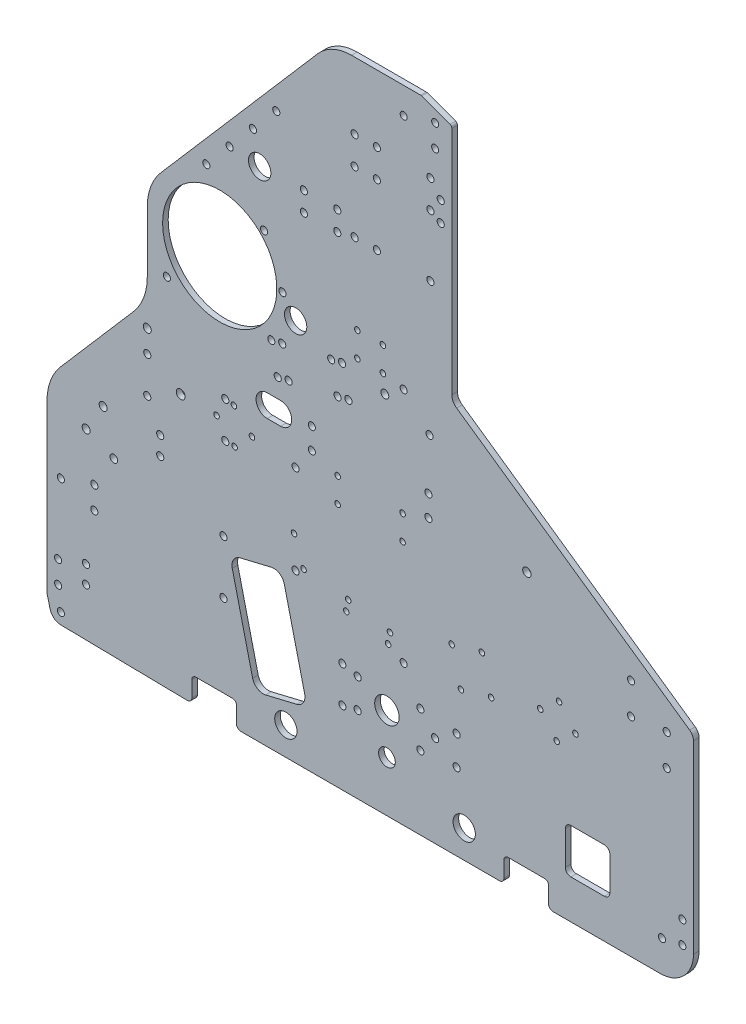
SolidWorks part; units mm, degrees
ref_plane "Front Plane" through (0, 0, 0) normal (0, 0, 1) x (1, 0, 0)
ref_plane "Top Plane" through (0, 0, 0) normal (0, 1, 0) x (1, 0, 0)
ref_plane "Right Plane" through (0, 0, 0) normal (1, 0, 0) x (0, 0, -1)
sketch "Sketch1" plane through (0, 0, 0) normal (0, 0, 1) x (1, 0, 0)
  line L0 (82.55, -20.32) -> (82.55, -6.35)
  line L2 (0, 0) -> (0, 157.48)
  line L4 (368.3, -20.32) -> (368.3, 106.68)
  line L5 (82.55, -6.35) -> (107.95, -6.35)
  line L6 (107.95, -6.35) -> (107.95, -20.32)
  line L7 (107.95, -20.32) -> (260.35, -20.32)
  line L8 (260.35, -20.32) -> (260.35, -6.35)
  line L9 (260.35, -6.35) -> (285.75, -6.35)
  line L10 (285.75, -6.35) -> (285.75, -20.32)
  line L11 (285.75, -20.32) -> (368.3, -20.32)
  line L12 (361.95, 12.7) -> (368.3, 12.7) construction
  line L13 (0, 0) -> (6.35, 0) construction
  line L14 (0.1896, -7.8901) -> (1.7771, -14.2401)
  line L15 (7.8295, -19.0491) -> (82.55, -20.32)
  line L16 (0, 0) -> (0, -6.35)
  line L17 (76.2, 128.905) -> (79.375, 128.905) construction
  line L18 (57.15, 118.5863) -> (101.6, 118.5862) construction
  line L19 (57.15, 118.5863) -> (57.15, 139.2238) construction
  line L20 (101.6, 118.5862) -> (101.6, 139.2237) construction
  line L21 (57.15, 139.2238) -> (101.6, 139.2237) construction
  line L22 (57.15, 118.5863) -> (101.6, 139.2237) construction
  line L23 (101.6, 118.5862) -> (57.15, 139.2238) construction
  line L24 (101.6, 139.2237) -> (125.4682, 147.9111) construction
  line L25 (203.2, 59.805) -> (203.2, 194.805) construction
  line L26 (203.2, 194.805) -> (203.2, 329.805) construction
  line L27 (355.6, 332.105) -> (330.2, 332.105) construction
  line L28 (330.2, 332.105) -> (330.2, 217.805) construction
  line L29 (330.2, 217.805) -> (355.6, 217.805) construction
  line L30 (355.6, 217.805) -> (355.6, 332.105) construction
  line L31 (203.2, 344.805) -> (203.2, 194.805) construction
  line L32 (50.8, 332.105) -> (76.2, 332.105) construction
  line L33 (76.2, 332.105) -> (76.2, 217.805) construction
  line L34 (50.8, 217.805) -> (50.8, 332.105) construction
  line L35 (76.2, 217.805) -> (50.8, 217.805) construction
  line L36 (213.2, 344.805) -> (230.6638, 338.455)
  line L37 (203.2, 344.805) -> (161.925, 344.805)
  line L38 (203.2, 344.805) -> (213.2, 344.805)
  line L39 (348.5362, 344.805) -> (413.4623, 344.805)
  line L40 (348.5362, 344.805) -> (230.6638, 344.805) construction
  line L42 (161.925, 344.805) -> (0, 157.48)
  line L44 (230.6638, 338.455) -> (230.6638, 202.565)
  line L45 (230.6638, 202.565) -> (368.3, 106.68)
  line L46 (213.2, 344.805) -> (-141.0713, 344.805) construction
  line L47 (350.3395, -2.3595) -> (368.3, -20.32) construction
  line L48 (125.4682, 147.9111) -> (133.0882, 147.9111) construction
  line L49 (125.4682, 154.2611) -> (133.0882, 154.2611)
  line L50 (125.4682, 141.5611) -> (133.0882, 141.5611)
  circle A0 centre (6.35, 0) radius 2.032
  circle A1 centre (6.35, 12.7) radius 2.032
  circle A2 centre (361.95, 0) radius 2.032
  circle A3 centre (361.95, 12.7) radius 2.032
  arc A5 (1.7771, -14.2401) -> (7.8295, -19.0491) centre (7.9375, -12.7) ccw
  circle A6 centre (7.9375, -12.7) radius 2.032
  arc A7 (0, -6.35) -> (0.1896, -7.8901) centre (6.35, -6.35) ccw
  circle A8 centre (38.1, 78.105) radius 2.032
  circle A9 centre (76.2, 128.905) radius 2.54
  circle A10 centre (101.6, 118.5862) radius 2.032
  circle A11 centre (101.6, 139.2237) radius 2.032
  circle A12 centre (57.15, 139.2238) radius 2.032
  circle A13 centre (57.15, 118.5863) radius 2.032
  circle A15 centre (203.2, 59.805) radius 2
  circle A16 centre (203.2, 194.805) radius 2
  circle A17 centre (203.2, 329.805) radius 2
  circle A18 centre (63.5, 313.055) radius 2.032
  circle A20 centre (355.6, 332.105) radius 2.032
  circle A21 centre (330.2, 332.105) radius 2.032
  circle A22 centre (355.6, 217.805) radius 2.032
  circle A23 centre (330.2, 217.805) radius 2.032
  circle A24 centre (50.8, 332.105) radius 2.032
  circle A25 centre (76.2, 332.105) radius 2.032
  circle A26 centre (50.8, 217.805) radius 2.032
  circle A27 centre (76.2, 217.805) radius 2.032
  circle A28 centre (221.1381, 335.28) radius 2
  circle A29 centre (224.3138, 298.831) radius 2.032
  circle A30 centre (353.06, 100.7351) radius 2.032
  circle A31 centre (332.74, 115.9751) radius 2.032
  circle A32 centre (332.74, 98.1951) radius 2.032
  circle A33 centre (353.06, 82.9551) radius 2.032
  circle A34 centre (117.3562, 280.4276) radius 2.032
  circle A35 centre (104.0678, 265.0548) radius 2.032
  circle A36 centre (90.7795, 249.682) radius 2.032
  circle A38 centre (130.6445, 295.8004) radius 2.032
  circle A39 centre (68.326, 182.9237) radius 2.032
  circle A40 centre (224.3138, 287.401) radius 2.032
  circle A41 centre (125.4682, 147.9111) radius 6.35
  circle A42 centre (221.1381, 322.58) radius 2
  circle A43 centre (350.3395, -2.3595) radius 2.032
  arc A44 (125.4682, 154.2611) -> (125.4682, 141.5611) centre (125.4682, 147.9111) ccw
  arc A45 (133.0882, 141.5611) -> (133.0882, 154.2611) centre (133.0882, 147.9111) ccw
  point P82 (203.2, 344.805)
  point P90 (368.3, 62.484)
  point P107 (129.2782, 147.9111)
  dimension "D6" = 4.064
  dimension "D10" = 6.35
  dimension "D11" = 4.064
  dimension "D17" = 38.1
  dimension "D27" = 4
  dimension "D31" = 4.064
  dimension "D32" = 41.275
  dimension "D36" = 4.064
  dimension "D47" = 39.624
  dimension "D48" = 4.064
  dimension "D25" = 5.08
  dimension "D26" = 4.064
  dimension "D52" = 4.064
  dimension "D65" = 4.064
  dimension "D69" = 4.064
  dimension "D72" = 12.7
  dimension "D77" = 6.35
  dimension "D2" = 127
  dimension "D3" = 13.97
  dimension "D4" = 25.4
  dimension "D5" = 152.4
  dimension "D7" = 12.7
  dimension "D8" = 6.35
  dimension "D9" = 20.32
  dimension "D12" = 12.7
  dimension "D13" = 1.5875
  dimension "D14" = 82.55
  dimension "D15" = 368.3
  dimension "D16" = 6.35
  dimension "D18" = 98.425
  dimension "D19" = 38.1
  dimension "D20" = 50.8
  dimension "D21" = 3.175
  dimension "D22" = 270
  dimension "D23" = 20.6375
  dimension "D24" = 44.45
  dimension "D28" = 135
  dimension "D29" = 12.7
  dimension "D30" = 15
  dimension "D33" = 63.5
  dimension "D34" = 27.4638
  dimension "D35" = 12.7
  dimension "D37" = 114.3
  dimension "D38" = 25.4
  dimension "D39" = 12.7
  dimension "D40" = 157.48
  dimension "D41" = 142.24
  dimension "D42" = 365.125
  dimension "D43" = 10
  dimension "D44" = 6.35
  dimension "D45" = 31.75
  dimension "D46" = 3.175
  dimension "D49" = 6.35
  dimension "D50" = 203.2
  dimension "D51" = 15.24
  dimension "D53" = 17.78
  dimension "D54" = 17.78
  dimension "D55" = 20.32
  dimension "D56" = 15.24
  dimension "D57" = 92.202
  dimension "D58" = 8.382
  dimension "D59" = 20.32
  dimension "D60" = 20.32
  dimension "D61" = 8.382
  dimension "D62" = 20.32
  dimension "D63" = 8.382
  dimension "D64" = 8.382
  dimension "D66" = 35.052
  dimension "D67" = 68.326
  dimension "D68" = 11.43
  dimension "D70" = 25.4
  dimension "D71" = 110
  dimension "D73" = 17.9381
  dimension "D74" = 12.7
  dimension "D75" = 45
  dimension "D76" = 25.4
  dimension "D79" = 7.62
extrude "Boss-Extrude1" add sketch "Sketch1" along normal blind 3.175 contours L16 A7 L14 A5 L15 L2 A0 A1 A6 region at (171.4194, 119.4541, 0)
fillet "Fillet1" radius 2.286 4 edges at (285.75, -6.35, 1.5875) (107.95, -6.35, 1.5875) (260.35, -6.35, 1.5875) (82.55, -6.35, 1.5875)
fillet "Fillet2" radius 6.35 1 edges at (230.6638, 202.565, 1.5875)
sketch "Sketch2" plane through (0, 0, 0) normal (0, 0, -1) x (-1, 0, 0)
  circle A0 centre (-100.5528, 71.086) radius 2.032 construction
  circle A1 centre (-100.5528, 40.606) radius 2.032 construction
  circle A2 centre (-22.225, 18.2025) radius 2.032 construction
  circle A3 centre (-22.225, 8.0425) radius 2.032 construction
  circle A4 centre (-100.5528, 71.086) radius 2.032
  circle A5 centre (-100.5528, 40.606) radius 2.032
  circle A6 centre (-22.225, 18.2025) radius 2.032
  circle A7 centre (-22.225, 8.0425) radius 2.032
extrude "Cut-Extrude1" cut sketch "Sketch2" against normal through all
fillet "Fillet3" radius 1.5875 2 edges at (230.6638, 338.455, 1.5875) (213.2, 344.805, 1.5875)
sketch "Sketch3" plane through (0, 0, 3.175) normal (0, 0, 1) x (1, 0, 0)
  line L0 (132.9524, 63.2646) -> (132.7215, 64.2281) construction
  line L1 (128.3814, 66.8897) -> (110.6828, 62.6472) construction
  line L2 (114.5132, 58.4237) -> (126.8822, 61.3887) construction
  line L3 (108.0212, 58.3071) -> (108.2522, 57.3436) construction
  line L4 (131.2006, 57.703) -> (140.0164, 20.9265) construction
  line L5 (144.0993, 16.7636) -> (132.9524, 63.2646) construction
  line L6 (108.2522, 57.3436) -> (119.3991, 10.8426) construction
  line L7 (121.1509, 16.4042) -> (112.3351, 53.1807) construction
  line L8 (119.3991, 10.8426) -> (119.6301, 9.8791) construction
  line L9 (144.3303, 15.8001) -> (144.0993, 16.7636) construction
  line L10 (137.8383, 15.6835) -> (125.4694, 12.7185) construction
  line L11 (123.9701, 7.2175) -> (141.6687, 11.4601) construction
  line L12 (132.9524, 63.2646) -> (132.7215, 64.2281)
  line L13 (128.3814, 66.8897) -> (110.6828, 62.6472)
  line L14 (114.5132, 58.4237) -> (126.8822, 61.3887)
  line L15 (108.0212, 58.3071) -> (108.2522, 57.3436)
  line L16 (131.2006, 57.703) -> (140.0164, 20.9265)
  line L17 (144.0993, 16.7636) -> (132.9524, 63.2646)
  line L18 (108.2522, 57.3436) -> (119.3991, 10.8426)
  line L19 (121.1509, 16.4042) -> (112.3351, 53.1807)
  line L20 (119.3991, 10.8426) -> (119.6301, 9.8791)
  line L21 (144.3303, 15.8001) -> (144.0993, 16.7636)
  line L22 (137.8383, 15.6835) -> (125.4694, 12.7185)
  line L23 (123.9701, 7.2175) -> (141.6687, 11.4601)
  line L24 (127.7894, 69.3598) -> (110.0908, 65.1172)
  line L25 (105.5512, 57.715) -> (105.7822, 56.7515)
  line L26 (105.7822, 56.7515) -> (116.9291, 10.2505)
  line L27 (116.9291, 10.2505) -> (117.16, 9.287)
  line L28 (124.5622, 4.7475) -> (142.2608, 8.99)
  line L29 (146.8003, 16.3922) -> (146.5694, 17.3557)
  line L30 (146.5694, 17.3557) -> (135.4225, 63.8567)
  line L31 (135.4225, 63.8567) -> (135.1915, 64.8202)
  line L32 (14.605, -0.1369) -> (103.7278, 32.3011) construction
  line L33 (14.605, -0.1369) -> (103.7278, 32.3011)
  line L34 (0, -6.35) -> (0, 157.48) construction
  line L35 (-39.6666, 74.7152) -> (103.7278, 126.9065) construction
  line L36 (26.9875, 46.9531) -> (26.9875, 59.6531) construction
  line L37 (107.95, -20.32) -> (260.35, -20.32) construction
  line L38 (64.5259, 92.5258) -> (64.5259, 102.9405) construction
  line L39 (131.6538, 14.201) -> (136.0946, -4.3242) construction
  line L40 (136.0946, -4.3242) -> (237.6946, -4.3242) construction
  arc A0 (132.7215, 64.2281) -> (128.6308, 66.9403) centre (129.2206, 63.3889) ccw construction
  arc A1 (110.6828, 62.6472) -> (110.4377, 62.5791) centre (111.522, 59.1463) ccw construction
  arc A2 (128.6308, 66.9403) -> (128.3814, 66.8897) centre (129.2206, 63.3889) ccw construction
  arc A3 (110.4377, 62.5791) -> (108.0212, 58.3071) centre (111.522, 59.1463) ccw construction
  arc A4 (119.6301, 9.8791) -> (123.7207, 7.1669) centre (123.1309, 10.7183) ccw construction
  arc A5 (141.9139, 11.5281) -> (144.3303, 15.8001) centre (140.8295, 14.9609) ccw construction
  arc A6 (141.6687, 11.4601) -> (141.9139, 11.5281) centre (140.8295, 14.9609) ccw construction
  arc A7 (123.7207, 7.1669) -> (123.9701, 7.2175) centre (123.1309, 10.7183) ccw construction
  arc A8 (132.7215, 64.2281) -> (128.6308, 66.9403) centre (129.2206, 63.3889) ccw
  arc A9 (110.6828, 62.6472) -> (110.4377, 62.5791) centre (111.522, 59.1463) ccw
  arc A10 (128.6308, 66.9403) -> (128.3814, 66.8897) centre (129.2206, 63.3889) ccw
  arc A11 (110.4377, 62.5791) -> (108.0212, 58.3071) centre (111.522, 59.1463) ccw
  arc A12 (119.6301, 9.8791) -> (123.7207, 7.1669) centre (123.1309, 10.7183) ccw
  arc A13 (141.9139, 11.5281) -> (144.3303, 15.8001) centre (140.8295, 14.9609) ccw
  arc A14 (141.6687, 11.4601) -> (141.9139, 11.5281) centre (140.8295, 14.9609) ccw
  arc A15 (123.7207, 7.1669) -> (123.9701, 7.2175) centre (123.1309, 10.7183) ccw
  arc A16 (110.0908, 65.1172) -> (109.6726, 65.0012) centre (111.522, 59.1463) ccw
  arc A17 (109.6726, 65.0012) -> (105.5512, 57.715) centre (111.522, 59.1463) ccw
  arc A18 (117.16, 9.287) -> (124.1369, 4.6613) centre (123.1309, 10.7183) ccw
  arc A19 (124.1369, 4.6613) -> (124.5622, 4.7475) centre (123.1309, 10.7183) ccw
  arc A20 (142.2608, 8.99) -> (142.6789, 9.1061) centre (140.8295, 14.9609) ccw
  arc A21 (142.6789, 9.1061) -> (146.8003, 16.3922) centre (140.8295, 14.9609) ccw
  arc A22 (135.1915, 64.8202) -> (128.2147, 69.446) centre (129.2206, 63.3889) ccw
  arc A23 (128.2147, 69.446) -> (127.7894, 69.3598) centre (129.2206, 63.3889) ccw
  circle A24 centre (136.0946, -4.3242) radius 6.35
  circle A25 centre (237.6946, -4.3242) radius 6.35
  circle A26 centre (134.1438, 208.2281) radius 2.032 construction
  circle A33 centre (26.9875, 46.9531) radius 2.032
  circle A34 centre (26.9875, 59.6531) radius 2.032
  circle A35 centre (7.9375, 53.3031) radius 2.032
  circle A37 centre (32.0306, 100.8109) radius 32.385 construction
  circle A38 centre (32.0306, 100.8109) radius 2.286
  circle A39 centre (123.682, 233.4851) radius 2.032 construction
  circle A40 centre (64.5259, 102.9405) radius 2.032
  circle A41 centre (64.5259, 92.5258) radius 2.032
  circle A42 centre (134.1438, 208.2281) radius 2.032
  circle A43 centre (123.682, 233.4851) radius 2.032
  ellipse E0 centre (124.5974, 48.8487) end of major axis (128.5376, 61.3578) minor radius 6 (131.2006, 57.703) -> (126.8822, 61.3887) ccw construction
  ellipse E1 centre (122.2349, 48.2824) end of major axis (113.0518, 57.6456) minor radius 6 (114.5132, 58.4237) -> (112.3351, 53.1807) ccw construction
  ellipse E2 centre (127.7541, 25.2585) end of major axis (131.6942, 37.7675) minor radius 6 (121.1509, 16.4042) -> (125.4694, 12.7185) ccw construction
  ellipse E3 centre (130.1166, 25.8248) end of major axis (139.2998, 16.4616) minor radius 6 (137.8383, 15.6835) -> (140.0164, 20.9265) ccw construction
  ellipse E4 centre (124.5974, 48.8487) end of major axis (120.6573, 36.3397) minor radius 6 (131.2006, 57.703) -> (126.8822, 61.3887) ccw
  ellipse E5 centre (122.2349, 48.2824) end of major axis (131.4181, 38.9192) minor radius 6 (114.5132, 58.4237) -> (112.3351, 53.1807) ccw
  ellipse E6 centre (127.7541, 25.2585) end of major axis (131.6942, 37.7675) minor radius 6 (121.1509, 16.4042) -> (125.4694, 12.7185) ccw
  ellipse E7 centre (130.1166, 25.8248) end of major axis (139.2998, 16.4616) minor radius 6 (137.8383, 15.6835) -> (140.0164, 20.9265) ccw
  point P93 (26.9875, 53.3031)
  point P115 (32.0306, 100.8109)
  dimension "D3" = 64.77
  dimension "D4" = 4.572
  dimension "D8" = 4.064
  dimension "D13" = 12.7
  dimension "D15" = 101.6
  dimension "D2" = 88.9
  dimension "D5" = 7.9375
  dimension "D6" = 19.05
  dimension "D7" = 73.6231
  dimension "D9" = 12.7
  dimension "D10" = 10.4147
  dimension "D11" = 37.5384
  dimension "D12" = 45.5727
  dimension "D14" = 19.05
  dimension "D1" = 2.54
extrude "Cut-Extrude2" cut sketch "Sketch3" against normal through all contours A22 A23 L24 A16 A17 L25 L26 L27 A18 A19 L28 A20 A21 L29 L30 L31 A15 A12 L20 L18 L15 A11 A9 L13 A10 A8 L12 L17 L21 A13 A14 L23 | A12 A15 L23 A14 A13 L21 L17 L12 A8 A10 L13 A9 A11 L15 L18 L20 E7 L22 E6 L19 E5 L14 E4 L16 | L22 E7 L16 E4 L14 E5 L19 E6 | A38 | A41 | A40 | A35 | A34 | A33 | A43 | A42 | A24 | A25 region at (137.844, 39.8506, 3.175) region at (126.1758, 37.0536, 3.175) region at (128.1544, 68.6507, 3.175) region at (32.0306, 100.8109, 3.175) region at (64.5259, 102.9405, 3.175) region at (64.5259, 92.5258, 3.175)
sketch "Sketch4" plane through (0, 0, 3.175) normal (0, 0, 1) x (1, 0, 0)
  line L0 (57.15, 139.2238) -> (101.6, 139.2237) construction
  line L1 (168.275, 21.4312) -> (212.725, 21.4312) construction
  line L2 (168.275, 21.4312) -> (168.275, 42.0687) construction
  line L3 (168.275, 42.0687) -> (212.725, 42.0687) construction
  line L4 (212.725, 21.4312) -> (212.725, 42.0687) construction
  line L5 (168.275, 21.4312) -> (212.725, 42.0687) construction
  line L6 (168.275, 42.0687) -> (212.725, 21.4312) construction
  line L7 (57.15, 118.5863) -> (57.15, 139.2238) construction
  line L8 (107.95, -20.32) -> (260.35, -20.32) construction
  line L9 (193.675, 31.75) -> (177.005, 31.75) construction
  line L10 (190.5, 31.75) -> (193.675, 31.75) construction
  line L11 (6.35, 12.7) -> (361.95, 12.7) construction
  line L12 (107.95, -6.35) -> (107.95, -20.32) construction
  line L13 (193.675, 31.75) -> (220.6625, 31.75) construction
  line L14 (177.005, 23.4569) -> (177.005, 40.0431) construction
  line L15 (213.2, 44.805) -> (193.2, 44.805) construction
  line L16 (213.2, 44.805) -> (213.2, 344.805) construction
  line L17 (213.2, 344.805) -> (193.2, 344.805) construction
  line L18 (193.2, 44.805) -> (193.2, 344.805) construction
  line L19 (213.2, 44.805) -> (193.2, 344.805) construction
  line L20 (213.2, 344.805) -> (193.2, 44.805) construction
  line L21 (226.1381, 335.28) -> (226.1381, 31.75) construction
  line L22 (237.33, 40.0431) -> (233.3612, 40.0431) construction
  line L23 (237.33, 23.4569) -> (233.3612, 23.4569) construction
  circle A0 centre (168.275, 42.0687) radius 2.032
  circle A1 centre (212.725, 42.0687) radius 2.032
  circle A2 centre (212.725, 21.4312) radius 2.032
  circle A3 centre (168.275, 21.4312) radius 2.032
  circle A4 centre (193.675, 31.75) radius 6.985
  circle A7 centre (220.6625, 31.75) radius 14.2875 construction
  circle A8 centre (193.675, 31.75) radius 12.7 construction
  circle A9 centre (177.005, 40.0431) radius 2.032
  circle A10 centre (177.005, 23.4569) radius 2.032
  circle A11 centre (237.33, 40.0431) radius 2.032 construction
  circle A12 centre (237.33, 23.4569) radius 2.032 construction
  circle A13 centre (193.675, 8.4667) radius 4.7625
  circle A14 centre (221.1381, 31.75) radius 2.032
  circle A15 centre (221.1381, 31.75) radius 5 construction
  circle A16 centre (221.1381, 335.28) radius 5 construction
  circle A17 centre (233.3612, 23.4569) radius 2.032
  circle A18 centre (233.3612, 40.0431) radius 2.032
  point P0 (190.5, 31.75)
  point P26 (203.2, 194.805)
  point P38 (177.005, 31.75)
  dimension "D1" = 4.064
  dimension "D4" = 13.97
  dimension "D7" = 9.525
  dimension "D10" = 25.4
  dimension "D11" = 28.575
  dimension "D16" = 10
  dimension "D17" = 4.064
  dimension "D18" = 10
  dimension "D2" = 52.07
  dimension "D3" = 3.175
  dimension "D5" = 82.55
  dimension "D6" = 26.9875
  dimension "D8" = 20
  dimension "D9" = 300
  dimension "D12" = 16.67
  dimension "D13" = 16.5862
  dimension "D14" = 60.325
  dimension "D15" = 23.2833
  dimension "D19" = 3.9688
extrude "Cut-Extrude3" cut sketch "Sketch4" against normal through all
sketch "Sketch5" plane through (0, 0, 0) normal (0, 0, -1) x (-1, 0, 0)
  line L0 (-57.15, 223.5947) -> (-57.15, 165.3337)
  line L1 (-161.925, 344.805) -> (-52.7201, 218.4699) construction
  line L2 (-57.15, 165.3337) -> (0, 99.219)
  line L3 (0, -6.35) -> (0, 157.48) construction
  line L4 (-147.864, -30.311) -> (-147.864, -16.0874)
  line L5 (-50.4199, 215.8089) -> (0, 157.48) construction
  line L6 (-57.15, 223.5947) -> (0, 157.48)
  line L7 (0, 157.48) -> (0, 99.219)
  line L8 (-98.425, 208.2281) -> (-141.6756, 197.9719) construction
  line L9 (-368.3, -20.32) -> (-368.3, 106.68) construction
  line L10 (-285.75, -20.32) -> (-368.3, -20.32) construction
  circle A0 centre (-98.425, 208.2281) radius 32.5437
  circle A1 centre (-141.6756, 197.9719) radius 6.35
  circle A3 centre (-273.4056, 139.7279) radius 2.39
  dimension "D3" = 65.0875
  dimension "D7" = 12.7
  dimension "D8" = 4.78
  dimension "D1" = 38.1
  dimension "D2" = 57.15
  dimension "D4" = 41.275
  dimension "D5" = 41.275
  dimension "D6" = 94.8944
  dimension "D9" = 22.2382
  dimension "D10" = 160.0479
  dimension "D11" = 11.6447
  dimension "D14" = 62.5
  dimension "D13" = 44.45
extrude "Cut-Extrude5" cut sketch "Sketch5" against normal through all contours A0 | L7 L6 L0 L2 | A3 | A1 region at (28.575, 161.4068, 0) region at (98.425, 208.2281, 0) region at (273.4056, 139.7279, 0)
fillet "Fillet4" radius 31.75 3 edges at (0, 99.219, 1.5875) (57.15, 165.3337, 1.5875) (57.15, 223.5947, 1.5875)
sketch "Sketch6" plane through (0, 0, 3.175) normal (0, 0, 1) x (1, 0, 0)
  line L0 (285.75, -20.32) -> (368.3, -20.32) construction
  line L1 (298.45, 27.305) -> (317.5, 27.305)
  line L2 (295.275, 24.13) -> (295.275, 5.08)
  line L3 (298.45, 1.905) -> (317.5, 1.905)
  line L4 (320.675, 24.13) -> (320.675, 5.08)
  line L5 (295.275, 27.305) -> (320.675, 1.905) construction
  line L6 (295.275, 1.905) -> (320.675, 27.305) construction
  line L7 (368.3, -20.32) -> (368.3, 106.68) construction
  arc A0 (295.275, 5.08) -> (298.45, 1.905) centre (298.45, 5.08) ccw
  arc A1 (317.5, 1.905) -> (320.675, 5.08) centre (317.5, 5.08) ccw
  arc A2 (317.5, 27.305) -> (320.675, 24.13) centre (317.5, 24.13) cw
  arc A3 (298.45, 27.305) -> (295.275, 24.13) centre (298.45, 24.13) ccw
  point P0 (307.975, 14.605)
  dimension "D2" = 3.175
  dimension "D1" = 25.4
  dimension "D3" = 22.225
  dimension "D4" = 47.625
extrude "Cut-Extrude6" cut sketch "Sketch6" against normal through all
fillet "Fillet5" radius 25.4 1 edges at (161.925, 344.805, 1.5875)
sketch "Sketch8" plane through (0, 0, 0) normal (0, 0, -1) x (-1, 0, 0)
  line L0 (-230.6638, 337.343) -> (-230.6638, 205.8802) construction
  line L1 (-230.6638, 255.905) -> (-175.26, 255.905) construction
  line L2 (-175.26, 255.905) -> (-175.26, 306.705) construction
  line L3 (-175.26, 306.705) -> (-230.6638, 306.705) construction
  line L4 (-173.5432, 344.805) -> (-212.9203, 344.805) construction
  line L7 (-107.95, -20.32) -> (-260.35, -20.32) construction
  circle A0 centre (-218.44, 290.83) radius 3.9687
  circle A1 centre (-218.44, 290.83) radius 2.032
  circle A2 centre (218.44, 265.7972) radius 3.9687
  circle A3 centre (218.44, 265.7972) radius 2.032
  circle A4 centre (-205.74, 290.83) radius 3.9687
  circle A5 centre (-205.74, 290.83) radius 2.032
  circle A6 centre (-187.96, 290.83) radius 3.9687
  circle A7 centre (-187.96, 290.83) radius 2.032
  circle A8 centre (-187.96, 306.705) radius 2.032
  circle A9 centre (-175.26, 290.83) radius 3.9687
  circle A10 centre (-175.26, 290.83) radius 2.032
  circle A11 centre (-205.74, 306.705) radius 2.032
  circle A13 centre (-205.74, 255.905) radius 2.032
  circle A14 centre (-187.96, 255.905) radius 2.032
  circle A16 centre (-218.44, 306.705) radius 2.032
  circle A17 centre (-175.26, 306.705) radius 2.032
  circle A18 centre (-175.26, 255.905) radius 2.032
  circle A19 centre (-218.44, 255.905) radius 2.032
  circle A20 centre (-218.44, 306.705) radius 3.9687
  circle A21 centre (-205.74, 306.705) radius 3.9687
  circle A22 centre (-175.26, 306.705) radius 3.9687
  circle A23 centre (-218.44, 255.905) radius 3.9687
  circle A24 centre (-205.74, 255.905) radius 3.9687
  circle A25 centre (-187.96, 255.905) radius 3.9687
  circle A26 centre (-175.26, 255.905) radius 3.9687
  circle A27 centre (-187.96, 306.705) radius 3.9687
  dimension "D1" = 7.9375
  dimension "D7" = 4.064
  dimension "D13" = 12.2237
  dimension "D2" = 12.2237
  dimension "D3" = 12.7
  dimension "D4" = 17.78
  dimension "D5" = 12.7
  dimension "D6" = 88.9
  dimension "D8" = 38.1
  dimension "D9" = 17.78
  dimension "D10" = 12.7
  dimension "D11" = 55.4037
  dimension "D12" = 12.7
  dimension "D14" = 311.15
extrude "Cut-Extrude7" cut sketch "Sketch8" against normal through all contours A16 | A17 | A18 | A19 | A8 | A14 | A1 | A7 | A10 region at (218.44, 306.705, 0) region at (175.26, 306.705, 0) region at (175.26, 255.905, 0) region at (218.44, 255.905, 0)
sketch "Sketch10" plane through (0, 0, 3.175) normal (0, 0, 1) x (1, 0, 0)
  circle A4 centre (141.6425, 74.6844) radius 2.032 construction
  circle A5 centre (141.6425, 125.4844) radius 2.032 construction
  circle A6 centre (141.6425, 74.6844) radius 2.032
  circle A7 centre (141.6425, 125.4844) radius 2.032
extrude "Cut-Extrude8" cut sketch "Sketch10" against normal through all
sketch "Sketch11" plane through (0, 0, 3.175) normal (0, 0, 1) x (1, 0, 0)
  ellipse E4 centre (150.8814, 138.43) end of major axis (150.8814, 140.462) minor radius 2.032
  ellipse E5 centre (150.8814, 150.495) end of major axis (150.8814, 152.527) minor radius 2.032
  ellipse E6 centre (217.3024, 150.495) end of major axis (217.3024, 152.527) minor radius 2.032
  ellipse E7 centre (217.3024, 138.43) end of major axis (217.3024, 140.462) minor radius 2.032
extrude "Cut-Extrude9" cut sketch "Sketch11" against normal through all
sketch "Sketch12" plane through (0, 0, 0) normal (0, 0, -1) x (-1, 0, 0)
  line L0 (-173.5432, 344.805) -> (-212.9203, 344.805) construction
  circle A0 centre (-165.4175, 264.635) radius 2.032
  circle A1 centre (-203.2, 329.805) radius 2 construction
  circle A2 centre (-165.4175, 253.5225) radius 2.032
  circle A3 centre (-146.3675, 253.5225) radius 2.032
  circle A4 centre (-146.3675, 264.635) radius 2.032
  dimension "D1" = 80.17
  dimension "D2" = 4.064
  dimension "D3" = 37.7825
  dimension "D4" = 11.1125
  dimension "D5" = 19.05
extrude "Cut-Extrude10" cut sketch "Sketch12" against normal through all
sketch "Sketch14" plane through (0, 0, 0) normal (0, 0, -1) x (-1, 0, 0)
  line L0 (-130.6445, 295.8004) -> (-121.1847, 263.6885) construction
  line L1 (-121.1847, 263.6885) -> (-90.7795, 249.682) construction
  line L2 (-154.3272, 336.0154) -> (-64.88, 232.5373) construction
  line L4 (-118.517, 269.4796) -> (-115.3937, 261.0208) construction
  line L5 (-118.517, 269.4796) -> (-126.9758, 266.3562) construction
  line L6 (-126.9758, 266.3562) -> (-123.8524, 257.8974) construction
  line L7 (-115.3937, 261.0208) -> (-123.8524, 257.8974) construction
  line L8 (-118.517, 269.4796) -> (-123.8524, 257.8974) construction
  line L9 (-126.9758, 266.3562) -> (-115.3937, 261.0208) construction
  circle A0 centre (-121.1847, 263.6885) radius 6.376
  dimension "D1" = 22.225
  dimension "D2" = 9.017
extrude "Cut-Extrude11" cut sketch "Sketch14" against normal through all
sketch "Sketch15" plane through (0, 0, 3.175) normal (0, 0, 1) x (1, 0, 0)
  line L0 (38.1, 78.105) -> (35.0376, 98.2034) construction
  line L1 (20.5874, 75.6997) -> (81.7263, 75.6997) construction
  line L2 (57.15, 139.2238) -> (57.15, 151.9238) construction
  line L3 (52.4937, 153.9549) -> (22.3594, 84.8727) construction
  line L4 (56.0505, 156.8833) -> (192.439, 187.1199) construction
  line L5 (52.4937, 153.9549) -> (37.8292, 107.1192) construction
  line L6 (20.5874, 75.6997) -> (38.1, 78.105) construction
  line L7 (35.0376, 98.2034) -> (37.8292, 107.1192) construction
  line L8 (20.5874, 75.6997) -> (22.3594, 84.8727) construction
  line L9 (38.1, 78.105) -> (17.7697, 78.105) construction
  line L10 (17.7697, 78.105) -> (21.6585, 86.5998) construction
  line L11 (21.6585, 86.5998) -> (52.4937, 153.9549) construction
  circle A0 centre (20.5874, 75.6997) radius 2.159 construction
  circle A1 centre (20.5874, 75.6997) radius 2.159 construction
  circle A2 centre (57.15, 139.2238) radius 2.032 construction
  circle A3 centre (57.15, 139.2238) radius 2.032 construction
  circle A4 centre (57.15, 151.9238) radius 2.286
  circle A5 centre (192.439, 187.1199) radius 2.286
  circle A6 centre (57.15, 151.9238) radius 5.08 construction
  circle A7 centre (38.1, 78.105) radius 2.159 construction
  circle A8 centre (38.1, 78.105) radius 2.159
  arc A9 (163.8737, 173.6806) -> (164.5125, 170.7993) centre (165.557, 172.5423) ccw construction
  arc A10 (173.4398, 172.7784) -> (172.801, 175.6597) centre (171.7565, 173.9167) ccw construction
  arc A11 (172.801, 175.6597) -> (173.4398, 172.7784) centre (171.7565, 173.9167) ccw construction
  arc A12 (164.5125, 170.7993) -> (163.8737, 173.6806) centre (165.557, 172.5423) ccw construction
  arc A13 (169.1589, 192.0883) -> (169.7976, 189.2071) centre (168.1143, 190.3453) ccw construction
  arc A14 (169.7976, 189.2071) -> (169.1589, 192.0883) centre (168.1143, 190.3453) ccw construction
  arc A15 (160.2316, 190.1092) -> (160.8704, 187.2279) centre (161.9149, 188.9709) ccw construction
  arc A16 (160.8704, 187.2279) -> (160.2316, 190.1092) centre (161.9149, 188.9709) ccw construction
  arc A17 (129.7766, 166.1214) -> (130.4154, 163.2402) centre (131.4599, 164.9832) ccw construction
  arc A18 (139.3426, 165.2193) -> (138.7039, 168.1005) centre (137.6593, 166.3576) ccw construction
  arc A19 (138.7039, 168.1005) -> (139.3426, 165.2193) centre (137.6593, 166.3576) ccw construction
  arc A20 (130.4154, 163.2402) -> (129.7766, 166.1214) centre (131.4599, 164.9832) ccw construction
  arc A21 (135.7005, 181.6479) -> (135.0617, 184.5292) centre (134.0172, 182.7862) ccw construction
  arc A22 (135.0617, 184.5292) -> (135.7005, 181.6479) centre (134.0172, 182.7862) ccw construction
  arc A23 (126.1345, 182.55) -> (126.7732, 179.6688) centre (127.8177, 181.4118) ccw construction
  arc A24 (126.7732, 179.6688) -> (126.1345, 182.55) centre (127.8177, 181.4118) ccw construction
  arc A25 (163.8737, 173.6806) -> (164.5125, 170.7993) centre (165.557, 172.5423) ccw
  arc A26 (173.4398, 172.7784) -> (172.801, 175.6597) centre (171.7565, 173.9167) ccw
  arc A27 (172.801, 175.6597) -> (173.4398, 172.7784) centre (171.7565, 173.9167) ccw
  arc A28 (164.5125, 170.7993) -> (163.8737, 173.6806) centre (165.557, 172.5423) ccw
  arc A29 (169.1589, 192.0883) -> (169.7976, 189.2071) centre (168.1143, 190.3453) ccw
  arc A30 (169.7976, 189.2071) -> (169.1589, 192.0883) centre (168.1143, 190.3453) ccw
  arc A31 (160.2316, 190.1092) -> (160.8704, 187.2279) centre (161.9149, 188.9709) ccw
  arc A32 (160.8704, 187.2279) -> (160.2316, 190.1092) centre (161.9149, 188.9709) ccw
  arc A33 (129.7766, 166.1214) -> (130.4154, 163.2402) centre (131.4599, 164.9832) ccw
  arc A34 (139.3426, 165.2193) -> (138.7039, 168.1005) centre (137.6593, 166.3576) ccw
  arc A35 (138.7039, 168.1005) -> (139.3426, 165.2193) centre (137.6593, 166.3576) ccw
  arc A36 (130.4154, 163.2402) -> (129.7766, 166.1214) centre (131.4599, 164.9832) ccw
  arc A37 (135.7005, 181.6479) -> (135.0617, 184.5292) centre (134.0172, 182.7862) ccw
  arc A38 (135.0617, 184.5292) -> (135.7005, 181.6479) centre (134.0172, 182.7862) ccw
  arc A39 (126.1345, 182.55) -> (126.7732, 179.6688) centre (127.8177, 181.4118) ccw
  arc A40 (126.7732, 179.6688) -> (126.1345, 182.55) centre (127.8177, 181.4118) ccw
  circle A41 centre (22.3594, 84.8727) radius 2.286 construction
  circle A42 centre (22.3594, 84.8727) radius 2.286
  point P39 (52.4937, 153.9549)
  dimension "D2" = 4.572
  dimension "D6" = 10.16
  dimension "D1" = 12.7
  dimension "D3" = 139.7
  dimension "D4" = 12.5
  dimension "D5" = 74.0778
  dimension "D7" = 49.0778
extrude "Cut-Extrude12" cut sketch "Sketch15" against normal through all
sketch "Sketch16" plane through (0, 0, 3.175) normal (0, 0, 1) x (1, 0, 0)
  circle A0 centre (98.425, 208.2281) radius 34.925 construction
  circle A1 centre (98.425, 208.2281) radius 34.925
  circle A2 centre (98.425, 208.2281) radius 36.195
  dimension "D1" = 1.27
fillet "Fillet7" radius 5.08 1 edges at (368.3, 106.68, 1.5875)
fillet "Fillet8" radius 2.54 4 edges at (82.55, -20.32, 1.5875) (107.95, -20.32, 1.5875) (260.35, -20.32, 1.5875) (285.75, -20.32, 1.5875)
sketch "Sketch17" plane through (0, 0, 3.175) normal (0, 0, 1) x (1, 0, 0)
  line L0 (230.6638, 337.343) -> (230.6638, 205.8802) construction
  line L1 (173.5432, 344.805) -> (212.9203, 344.805) construction
  circle A0 centre (217.9638, 179.705) radius 2.032
  dimension "D1" = 12.7
  dimension "D3" = 4.064
  dimension "D2" = 165.1
extrude "Cut-Extrude13" cut sketch "Sketch17" against normal through all contours A0
fillet "Fillet9" radius 19.05 1 edges at (368.3, -20.32, 1.5875)
sketch "Sketch18" plane through (0, 0, 3.175) normal (0, 0, 1) x (1, 0, 0)
  line L0 (150.8814, 138.43) -> (217.3024, 138.43) construction
  line L1 (184.0919, 138.43) -> (184.0919, 119.38) construction
  line L2 (165.5919, 119.38) -> (202.5919, 119.38) construction
  line L3 (184.0919, 138.43) -> (184.0919, 210.82) construction
  line L4 (176.8148, 210.82) -> (191.369, 210.82) construction
  line L5 (184.0919, 138.43) -> (184.0919, 65.405) construction
  line L6 (194.31, -20.32) -> (194.31, 64.77) construction
  line L7 (244.4169, 65.405) -> (184.0919, 65.405) construction
  line L8 (253.004, 67.7059) -> (235.8298, 63.1041) construction
  line L9 (202.5919, 133.35) -> (165.5919, 133.35) construction
  line L10 (230.5706, 82.7317) -> (247.7448, 87.3335) construction
  line L11 (244.4169, 65.405) -> (239.1577, 85.0326) construction
  line L12 (184.0919, 119.38) -> (143.4519, 119.38) construction
  line L13 (143.4519, 119.38) -> (143.4519, 85.09) construction
  line L14 (146.1667, 77.6312) -> (140.7371, 92.5488) construction
  line L15 (184.0919, 138.43) -> (116.7819, 138.43) construction
  line L16 (116.7819, 138.43) -> (116.7819, 128.27) construction
  line L17 (116.7819, 128.27) -> (106.4905, 138.5614) construction
  line L18 (111.6362, 133.4157) -> (101.7579, 123.5374) construction
  line L19 (184.0919, 138.43) -> (285.6919, 138.43) construction
  line L20 (285.6919, 138.43) -> (285.6919, 70.485) construction
  line L21 (290.3695, 64.9104) -> (281.0143, 76.0596) construction
  line L22 (96.6123, 128.6831) -> (106.9036, 118.3917) construction
  line L23 (184.0919, 210.82) -> (184.0919, 196.85) construction
  line L24 (176.8148, 196.85) -> (191.369, 196.85) construction
  line L25 (285.6919, 70.485) -> (296.3936, 79.4647) construction
  line L26 (291.7159, 85.0393) -> (301.0712, 73.8902) construction
  line L27 (110.49, -20.32) -> (257.81, -20.32) construction
  line L28 (107.95, -8.636) -> (107.95, -17.78) construction
  line L29 (194.31, 64.77) -> (170.511, 68.9664) construction
  line L30 (170.511, 68.9664) -> (171.6137, 75.2199) construction
  line L31 (194.31, 64.77) -> (195.4127, 71.0235) construction
  circle A0 centre (170.511, 68.9664) radius 1.5875
  circle A1 centre (150.8814, 138.43) radius 2.032 construction
  circle A2 centre (217.3024, 138.43) radius 2.032 construction
  circle A3 centre (150.8814, 138.43) radius 2.032
  circle A4 centre (217.3024, 138.43) radius 2.032
  circle A5 centre (165.5919, 119.38) radius 1.5875
  circle A6 centre (202.5919, 119.38) radius 1.5875
  circle A7 centre (176.8148, 210.82) radius 1.5875
  circle A8 centre (191.369, 210.82) radius 1.5875
  circle A9 centre (165.5919, 133.35) radius 1.5875
  circle A10 centre (202.5919, 133.35) radius 1.5875
  circle A11 centre (235.8298, 63.1041) radius 1.5875
  circle A12 centre (253.004, 67.7059) radius 1.5875
  circle A13 centre (230.5706, 82.7317) radius 1.5875
  circle A14 centre (247.7448, 87.3335) radius 1.5875
  circle A15 centre (140.7371, 92.5488) radius 1.5875
  circle A16 centre (146.1667, 77.6312) radius 1.5875
  circle A17 centre (116.7819, 128.27) radius 1.5875
  circle A18 centre (106.4905, 138.5614) radius 1.5875
  circle A20 centre (281.0143, 76.0596) radius 1.5875
  circle A21 centre (290.3695, 64.9104) radius 1.5875
  circle A22 centre (96.6123, 128.6831) radius 1.5875
  circle A23 centre (106.9036, 118.3917) radius 1.5875
  circle A24 centre (176.8148, 196.85) radius 1.5875
  circle A25 centre (191.369, 196.85) radius 1.5875
  circle A26 centre (291.7159, 85.0393) radius 1.5875
  circle A27 centre (301.0712, 73.8902) radius 1.5875
  circle A28 centre (194.31, 64.77) radius 1.5875
  circle A29 centre (171.6137, 75.2199) radius 1.5875
  circle A30 centre (195.4127, 71.0235) radius 1.5875
  point P3 (184.0919, 119.38)
  point P17 (184.0919, 210.82)
  point P24 (244.4169, 65.405)
  point P27 (184.0919, 133.35)
  point P41 (143.4519, 85.09)
  point P55 (285.6919, 70.485)
  point P60 (101.7579, 123.5374)
  point P66 (184.0919, 196.85)
  point P72 (296.3936, 79.4647)
  dimension "D3" = 3.175
  dimension "D6" = 73.025
  dimension "D8" = 13.97
  dimension "D11" = 20.32
  dimension "D12" = 40.64
  dimension "D14" = 15.875
  dimension "D18" = 45
  dimension "D23" = 14.5542
  dimension "D20" = 13.97
  dimension "D25" = 13.97
  dimension "D26" = 13.97
  dimension "D29" = 3.175
  dimension "D32" = 6.35
  dimension "D1" = 19.05
  dimension "D2" = 37
  dimension "D4" = 72.39
  dimension "D5" = 14.5542
  dimension "D7" = 60.325
  dimension "D9" = 17.78
  dimension "D10" = 75
  dimension "D13" = 34.29
  dimension "D15" = 20
  dimension "D16" = 67.31
  dimension "D17" = 10.16
  dimension "D19" = 14.5542
  dimension "D21" = 101.6
  dimension "D22" = 67.945
  dimension "D24" = 40
  dimension "D27" = 85.09
  dimension "D28" = 86.36
  dimension "D30" = 24.1661
  dimension "D31" = 100
extrude "Cut-Extrude14" cut sketch "Sketch18" against normal through all contours A6 | A5 | A12 | A11 | A13 | A14 | A10 | A9 | A7 | A8 | A16 | A15 | A18 | A17 | A20 | A21 | A27 | A26 | A23 | A22 | A24 | A25 | A28 | A0 | A29 | A30
equation "\"D7@Sketch15\"=\"D5@Sketch15\"-25mm"
